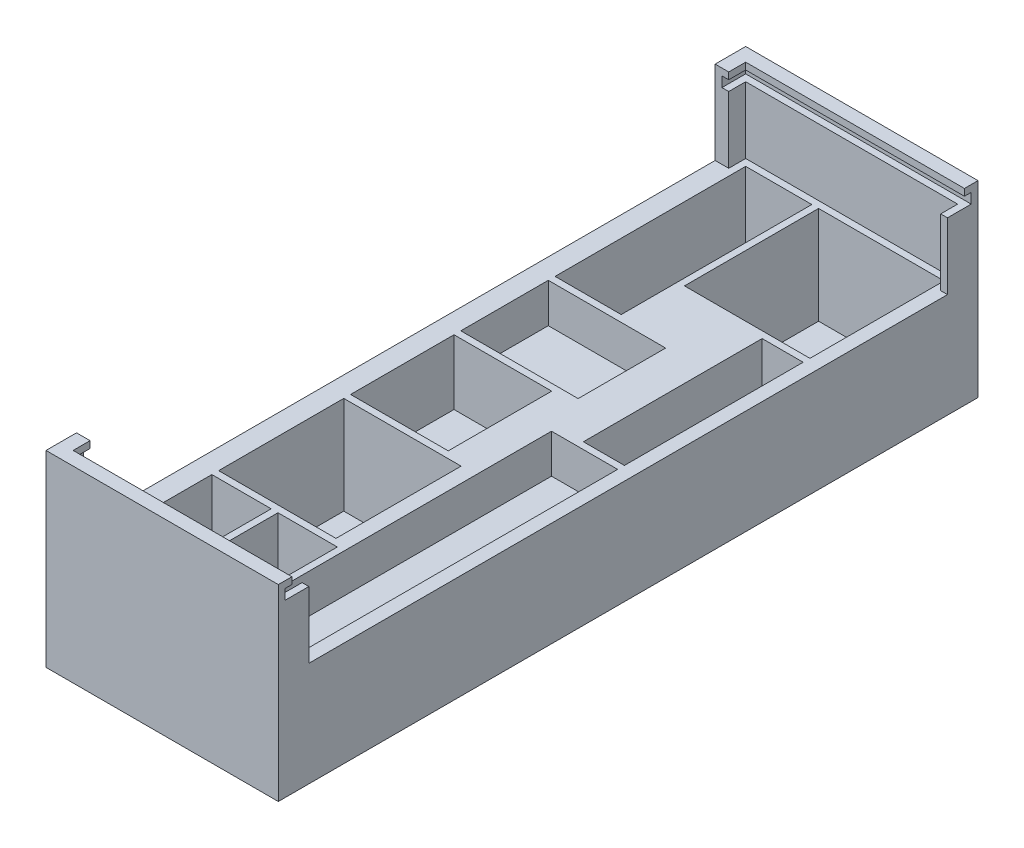
SolidWorks part; units mm, degrees
ref_plane "Front Plane" through (0, 0, 0) normal (0, 0, 1) x (1, 0, 0)
ref_plane "Top Plane" through (0, 0, 0) normal (0, 1, 0) x (1, 0, 0)
ref_plane "Right Plane" through (0, 0, 0) normal (1, 0, 0) x (0, 0, -1)
sketch "Sketch1" plane through (0, 0, 0) normal (0, 1, 0) x (1, 0, 0)
  line L0 (34.25, 101.15) -> (-32.25, 101.15)
  line L1 (-34.25, -103.15) -> (34.25, -103.15)
  line L2 (-34.25, -103.15) -> (-34.25, 103.15)
  line L3 (-34.25, 103.15) -> (34.25, 103.15)
  line L4 (34.25, -103.15) -> (34.25, 103.15)
  line L5 (-34.25, -103.15) -> (34.25, 103.15) construction
  line L6 (-34.25, 103.15) -> (34.25, -103.15) construction
  line L7 (-32.25, 101.15) -> (-32.25, -101.15)
  line L8 (-32.25, -101.15) -> (34.25, -101.15)
  line L9 (-30.25, 94.15) -> (-34.25, 94.15)
  line L10 (-30.25, -99.15) -> (32.25, -99.15)
  line L11 (-30.25, -99.15) -> (-30.25, 99.15)
  line L12 (-30.25, 99.15) -> (32.25, 99.15)
  line L13 (32.25, -99.15) -> (32.25, 99.15)
  line L14 (-30.25, -99.15) -> (32.25, 99.15) construction
  line L15 (-30.25, 99.15) -> (32.25, -99.15) construction
  line L16 (-30.25, -94.15) -> (-34.25, -94.15)
  line L17 (32.25, 94.15) -> (34.25, 94.15)
  line L18 (32.25, -94.15) -> (34.25, -94.15)
  line L20 (-28.25, -60.25) -> (-10.75, -60.25)
  line L21 (-28.25, -60.25) -> (-28.25, -97.15)
  line L22 (-28.25, -97.15) -> (-10.75, -97.15)
  line L23 (-10.75, -60.25) -> (-10.75, -97.15)
  line L24 (-8.75, -60.25) -> (8.75, -60.25)
  line L25 (-8.75, -60.25) -> (-8.75, -97.15)
  line L26 (-8.75, -97.15) -> (8.75, -97.15)
  line L27 (8.75, -60.25) -> (8.75, -97.15)
  line L28 (10.75, -90.4) -> (30.25, -90.4)
  line L29 (10.75, -90.4) -> (10.75, 0.9)
  line L30 (10.75, 0.9) -> (30.25, 0.9)
  line L31 (30.25, -90.4) -> (30.25, 0.9)
  line L36 (-28.25, -58.25) -> (6.35, -58.25)
  line L37 (-28.25, -58.25) -> (-28.25, -21.35)
  line L38 (-28.25, -21.35) -> (6.35, -21.35)
  line L39 (6.35, -58.25) -> (6.35, -21.35)
  line L40 (-28.25, 13.15) -> (6.35, 13.15)
  line L41 (-28.25, 13.15) -> (-28.25, 38.95)
  line L42 (-28.25, 38.95) -> (6.35, 38.95)
  line L43 (6.35, 13.15) -> (6.35, 38.95)
  line L44 (-28.25, -19.35) -> (0.55, -19.35)
  line L45 (-28.25, -19.35) -> (-28.25, 11.15)
  line L46 (-28.25, 11.15) -> (0.55, 11.15)
  line L47 (0.55, -19.35) -> (0.55, 11.15)
  line L48 (-28.25, 40.95) -> (-8.75, 40.95)
  line L49 (-28.25, 40.95) -> (-28.25, 97.15)
  line L50 (-28.25, 97.15) -> (-8.75, 97.15)
  line L51 (-8.75, 40.95) -> (-8.75, 97.15)
  line L52 (18.15, 55.6) -> (30.25, 55.6)
  line L53 (18.15, 55.6) -> (18.15, 2.9)
  line L54 (18.15, 2.9) -> (30.25, 2.9)
  line L55 (30.25, 55.6) -> (30.25, 2.9)
  line L56 (29.25, -90.4) -> (29.25, -97.15)
  line L58 (-6.75, 97.15) -> (30.25, 97.15)
  line L59 (-6.75, 97.15) -> (-6.75, 57.6)
  line L60 (-6.75, 57.6) -> (30.25, 57.6)
  line L61 (30.25, 97.15) -> (30.25, 57.6)
  point P0 (0, 0)
  point P10 (1, 0)
  point P60 (-8.75, 69.05)
  dimension "D1" = 206.3
  dimension "D2" = 68.5
  dimension "D3" = 2
  dimension "D4" = 2
  dimension "D5" = 2
  dimension "D6" = 2
  dimension "D7" = 2
  dimension "D8" = 2
  dimension "D9" = 2
  dimension "D10" = 9
  dimension "D11" = 9
  dimension "D12" = 2
  dimension "D13" = 2
  dimension "D14" = 36.9
  dimension "D15" = 17.5
  dimension "D16" = 2
  dimension "D17" = 17.5
  dimension "D19" = 19.5
  dimension "D20" = 2
  dimension "D22" = 2
  dimension "D23" = 36.9
  dimension "D24" = 34.6
  dimension "D25" = 25.8
  dimension "D26" = 34.6
  dimension "D27" = 2
  dimension "D28" = 2
  dimension "D29" = 2
  dimension "D30" = 30.5
  dimension "D31" = 56.2
  dimension "D32" = 19.5
  dimension "D33" = 28.8
  dimension "D34" = 12.1
  dimension "D35" = 52.7
  dimension "D37" = 91.3
  dimension "D40" = 2
  dimension "D41" = 2
  dimension "D42" = 2
extrude "Boss-Extrude3" add sketch "Sketch1<4>" along normal blind 2 separate body contours L48 L51 L50 L49 region at (-18.5, 0, -69.05)
sketch "Sketch1<4>" plane through (0, 0, 0) normal (0, 1, 0) x (1, 0, 0) same geometry as "Sketch1"
extrude "Boss-Extrude4" add sketch "Sketch1<5>" along normal blind 13.8 separate body contours L55 L52 L53 L54 region at (24.2, 0, -29.25)
sketch "Sketch1<5>" plane through (0, 0, 0) normal (0, 1, 0) x (1, 0, 0) same geometry as "Sketch1"
extrude "Boss-Extrude5" add sketch "Sketch1" along normal blind 17.3 separate body contours L28 L31 L30 L29 region at (20.5, 0, 44.75)
extrude "Boss-Extrude7" add sketch "Sketch1<8>" along normal blind 17.2 separate body contours L40 L43 L42 L41 region at (-10.95, 0, -26.05)
sketch "Sketch1<8>" plane through (0, 0, 0) normal (0, 1, 0) x (1, 0, 0) same geometry as "Sketch1"
extrude "Boss-Extrude8" add sketch "Sketch1<9>" along normal blind 9.7 separate body contours L44 L47 L46 L45 region at (-13.85, 0, 4.1)
sketch "Sketch1<9>" plane through (0, 0, 0) normal (0, 1, 0) x (1, 0, 0) same geometry as "Sketch1"
extrude "Boss-Extrude9" add sketch "Sketch1<10>" along normal blind 28.792 contours L10 L13 L12 L11 L51 L48 L49 L50 L47 L44 L45 L46 L43 L40 L41 L42 L39 L36 L37 L38 L31 L28 L29 L30 L20 L23 L22 L21 L24 L27 L26 L25 L52 L55 L54 L53 | L13 L18 L4 L17 | L16 L11 L9 L7 | L16 L7 L9 L2 region at (33.25, 0, 0) region at (-31.25, 0, 0) region at (-33.25, 0, 0) region at (3.9185, 0, -1.5997)
sketch "Sketch1<10>" plane through (0, 0, 0) normal (0, 1, 0) x (1, 0, 0) same geometry as "Sketch1"
extrude "Boss-Extrude10" add sketch "Sketch1<11>" along normal blind 48.4 contours L18 L13 L10 L11 L16 L7 L8 L4 | L13 L17 L4 L0 L7 L9 L11 L12 region at (1, 0, -99.6925) region at (1, 0, 99.6925)
sketch "Sketch1<11>" plane through (0, 0, 0) normal (0, 1, 0) x (1, 0, 0) same geometry as "Sketch1"
extrude "Boss-Extrude11" add sketch "Sketch1<12>" along normal blind 53.4 contours L7 L16 L2 L1 L4 L8 | L9 L7 L0 L4 L3 L2 region at (-3.0828, 0, -101.7328) region at (-3.0828, 0, 101.7328)
sketch "Sketch1<12>" plane through (0, 0, 0) normal (0, 1, 0) x (1, 0, 0) same geometry as "Sketch1"
sketch "Sketch2" plane through (0, 53.4, 0) normal (0, 1, 0) x (1, 0, 0)
  line L0 (-32.25, -94.15) -> (-32.25, -101.15)
  line L1 (-32.25, -101.15) -> (34.25, -101.15)
  line L2 (34.25, -101.15) -> (34.25, -99.15)
  line L3 (34.25, -99.15) -> (-30.25, -99.15)
  line L4 (-30.25, -99.15) -> (-30.25, -94.15)
  line L5 (-30.25, -94.15) -> (-32.25, -94.15)
  line L6 (-32.25, 94.15) -> (-32.25, 101.15)
  line L7 (-32.25, 101.15) -> (34.25, 101.15)
  line L8 (34.25, 101.15) -> (34.25, 99.15)
  line L9 (34.25, 99.15) -> (-30.25, 99.15)
  line L10 (-30.25, 99.15) -> (-30.25, 94.15)
  line L11 (-30.25, 94.15) -> (-32.25, 94.15)
  line L12 (34.25, 101.15) -> (-32.25, 101.15) construction
  line L13 (-32.25, -101.15) -> (34.25, -101.15) construction
  point P20 (-32.25, -97.65)
  dimension "D1" = 2
  dimension "D2" = 2
  dimension "D3" = 2
  dimension "D4" = 2
extrude "Boss-Extrude12" add sketch "Sketch2" against normal blind 2
extrude "Boss-Extrude13" add sketch "Sketch1<13>" against normal blind 2 contours L7 L16 L2 L1 L4 L8 | L18 L13 L10 L11 L16 L7 L8 L4 | L10 L13 L12 L11 L51 L48 L49 L50 L47 L44 L45 L46 L43 L40 L41 L42 L39 L36 L37 L38 L31 L28 L29 L30 L20 L23 L22 L21 L24 L27 L26 L25 L52 L55 L54 L53 | L28 L31 L30 L29 | L13 L18 L4 L17 | L16 L11 L9 L7 | L16 L7 L9 L2 | L23 L20 L21 L22 | L27 L24 L25 L26 | L36 L39 L38 L37 | L44 L47 L46 L45 | L40 L43 L42 L41 | L55 L52 L53 L54 | L61 L58 L59 L60 | L48 L51 L50 L49 | L9 L7 L0 L4 L3 L2 | L13 L17 L4 L0 L7 L9 L11 L12 region at (1, 0, -99.6925) region at (-3.0828, 0, -101.7328) region at (33.25, 0, 0) region at (-31.25, 0, 0) region at (-33.25, 0, 0) region at (1, 0, 99.6925) region at (3.9185, 0, -1.5997) region at (-3.0828, 0, 101.7328) region at (-19.5, 0, 78.7) region at (0, 0, 78.7) region at (20.5, 0, 44.75) region at (-10.95, 0, 39.8) region at (-10.95, 0, -26.05) region at (-13.85, 0, 4.1) region at (-18.5, 0, -69.05) region at (24.2, 0, -29.25) region at (11.75, 0, -77.375)
sketch "Sketch1<13>" plane through (0, 0, 0) normal (0, 1, 0) x (1, 0, 0) same geometry as "Sketch1"
